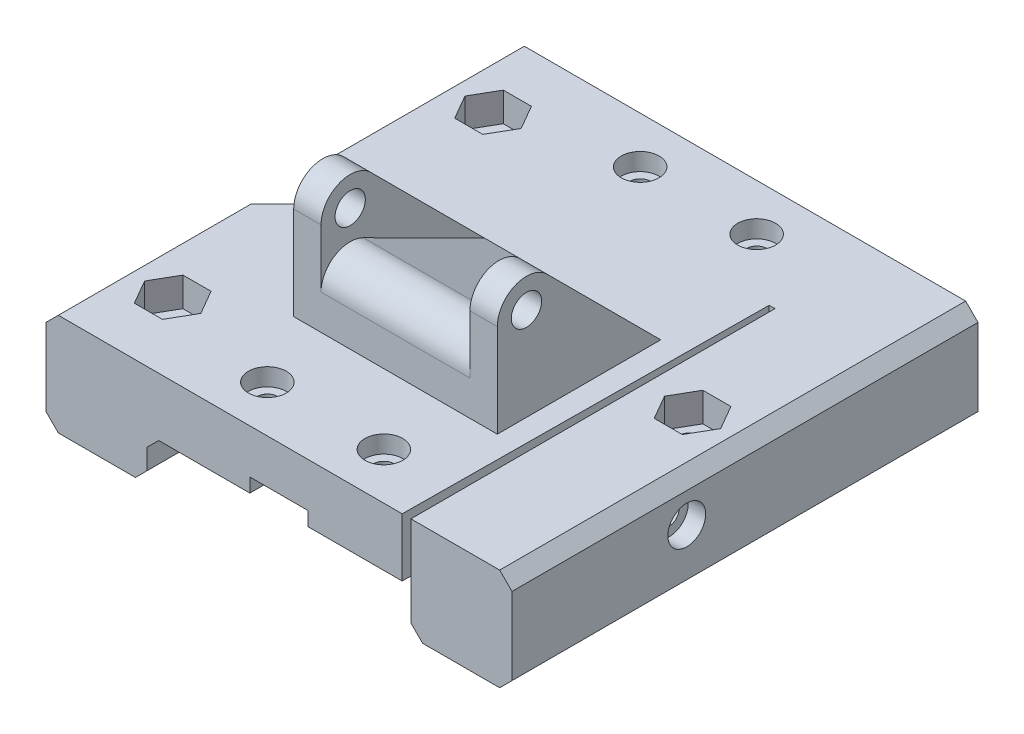
SolidWorks part; units mm, degrees
ref_plane "Front Plane" through (0, 0, 0) normal (0, 0, 1) x (1, 0, 0)
ref_plane "Top Plane" through (0, 0, 0) normal (0, 1, 0) x (1, 0, 0)
ref_plane "Right Plane" through (0, 0, 0) normal (1, 0, 0) x (0, 0, -1)
sketch "Sketch1" plane through (0, 0, 0) normal (0, 0, 1) x (1, 0, 0)
  line L0 (253.1831, 132.1321) -> (251.1831, 130.1321)
  line L1 (296.4801, 132.1321) -> (296.4801, 126.6321)
  line L2 (251.1831, 130.1321) -> (251.1831, 126.6321)
  line L3 (249.1831, 124.6321) -> (251.1831, 126.6321)
  line L4 (296.4801, 126.6321) -> (298.4801, 124.6321)
  line L949 (253.1831, 132.1321) -> (296.4801, 132.1321)
  line L950 (235.9482, 142.1321) -> (311.7151, 142.1321)
  line L1018 (235.9482, 124.6321) -> (249.1831, 124.6321)
  line L1037 (311.7151, 124.6321) -> (298.4801, 124.6321)
  line L1179 (235.9482, 124.6321) -> (233.8316, 126.7487)
  line L1180 (235.9482, 142.1321) -> (233.8316, 140.0155)
  line L1183 (311.7151, 124.6321) -> (313.8316, 126.7487)
  line L1184 (311.7151, 142.1321) -> (313.8316, 140.0155)
  line L1219 (233.8316, 126.7487) -> (233.8316, 140.0155)
  line L1220 (313.8316, 140.0155) -> (313.8316, 126.7487)
  point P2 (296.4801, 132.1321)
  point P3 (296.4801, 124.6321)
  point P4 (251.1831, 132.1321)
  point P5 (251.1831, 124.6321)
  dimension "D1" = 17.5
  dimension "D3" = 2
  dimension "D4" = 2
  dimension "D5" = 2
  dimension "D2" = 17.5
extrude "Boss-Extrude1" add sketch "Sketch1" along normal blind 80
sketch "Sketch2" plane through (0, 142.1321, 0) normal (0, 1, 0) x (1, 0, 0)
  line L0 (273.8316, 0) -> (273.8316, -80) construction
  line L3 (238.4807, -40) -> (314.2475, -40) construction
  circle A0 centre (243.0816, -12.5) radius 2.6
  circle A1 centre (304.5816, -40) radius 2.6
  circle A3 centre (243.0816, -67.5) radius 2.6
  dimension "D1" = 5.2
  dimension "D2" = 30.75
  dimension "D3" = 30.75
extrude "Cut-Extrude1" cut sketch "Sketch2" against normal through all
sketch "Sketch3" plane through (0, 132.1321, 0) normal (0, -1, 0) x (1, 0, 0)
  line L0 (296.4802, 80) -> (294.9802, 80)
  line L1 (296.4801, 80) -> (296.4801, 0) construction
  line L2 (296.4801, 17.5) -> (295.4801, 17.508)
  line L3 (296.4801, 17.5) -> (296.4802, 80)
  line L4 (294.9802, 80) -> (296.4802, 80)
  line L5 (295.4801, 17.508) -> (294.9802, 80)
  point P0 (296.4801, 80)
  point P4 (296.9801, 80.5)
  point P15 (296.9801, 17)
  point P16 (294.9801, 17)
  point P17 (294.9801, 80.5)
  point P19 (296.9801, 80)
  point P20 (296.9762, 17)
  point P22 (297.4841, 80.496)
  point P24 (295.4842, 80.512)
  point P25 (294.9802, 17.512)
  dimension "D1" = 1.5
  dimension "D2" = 1
sketch "Sketch5" plane through (313.8316, 0, 0) normal (1, 0, 0) x (0, 0, -1)
  line L0 (-40, 142.1321) -> (-40, 124.6321) construction
  line L2 (-80, 124.6321) -> (0, 124.6321) construction
  circle A0 centre (-50, 134.9015) radius 3.25
  dimension "D1" = 6.5
  dimension "D2" = 30
  dimension "D3" = 5.114
sketch "Sketch7" plane through (0, 132.1321, 0) normal (0, -1, 0) x (1, 0, 0)
  line L0 (291.4801, 52.875) -> (291.4801, 47.125)
  line L1 (291.4801, 47.125) -> (289.5801, 47.125)
  line L2 (289.5801, 47.125) -> (289.5801, 52.875)
  line L3 (289.5801, 52.875) -> (291.4801, 52.875)
  line L4 (260.0782, 50) -> (295.472, 50) construction
  line L5 (258.0836, 42.875) -> (258.0836, 37.125)
  line L6 (233.8316, 40) -> (313.8316, 40) construction
  line L7 (233.8316, 80) -> (233.8316, 0) construction
  line L8 (313.8316, 80) -> (313.8316, 0) construction
  line L9 (258.0836, 37.125) -> (256.1836, 37.125)
  line L10 (256.1836, 37.125) -> (256.1836, 42.875)
  line L11 (256.1836, 42.875) -> (258.0836, 42.875)
  line L12 (256.1836, 40) -> (258.0836, 40) construction
  line L13 (291.4801, 72.125) -> (291.4801, 50) construction
  dimension "D1" = 5.75
  dimension "D2" = 1.9
  dimension "D3" = 30
  dimension "D4" = 22.3515
  dimension "D5" = 22.352
extrude "Cut-Extrude5" cut sketch "Sketch7" against normal blind 5.75
sketch "Sketch9" plane through (0, 132.1321, 0) normal (0, -1, 0) x (1, 0, 0)
  line L0 (268.8316, 80) -> (268.8316, 60)
  line L1 (268.8316, 0) -> (278.8316, 0)
  line L2 (268.8316, 60) -> (278.8316, 60)
  line L3 (278.8316, 60) -> (278.8316, 80)
  line L4 (268.8316, 80) -> (278.8316, 80)
  line L5 (233.8316, 40) -> (313.8316, 40) construction
  line L6 (233.8316, 80) -> (233.8316, 0) construction
  line L7 (313.8316, 80) -> (313.8316, 0) construction
  line L8 (273.8316, 40) -> (273.8316, 79.96) construction
  line L9 (278.8316, 20) -> (278.8316, 0)
  line L10 (268.8316, 20) -> (278.8316, 20)
  line L11 (268.8316, 0) -> (268.8316, 20)
  dimension "D1" = 20
  dimension "D2" = 10
extrude "Cut-Extrude6" cut sketch "Sketch9" against normal blind 2.4
sketch "Sketch11" plane through (0, 132.1321, 0) normal (0, -1, 0) x (1, 0, 0)
  line L0 (273.8316, 79.96) -> (273.8316, 0.04) construction
  line L4 (233.8316, 80) -> (233.8316, 0) construction
  line L5 (233.8316, 40) -> (313.8316, 40) construction
  line L6 (313.8316, 80) -> (313.8316, 0) construction
  line L8 (235.9482, 80) -> (249.1831, 80) construction
  circle A0 centre (263.8316, 72) radius 1.75
  circle A1 centre (283.8316, 72) radius 1.75
  circle A2 centre (283.8316, 8) radius 1.75
  circle A3 centre (263.8316, 8) radius 1.75
  dimension "D1" = 3.5
  dimension "D2" = 8
  dimension "D3" = 10
extrude "Cut-Extrude7" cut sketch "Sketch11" against normal up to vertex
sketch "Sketch13" plane through (0, 142.1321, 0) normal (0, 1, 0) x (1, 0, 0)
  line L0 (263.8316, -8) -> (283.8316, -8) construction
  line L1 (273.8316, -8) -> (273.8316, -80) construction
  line L3 (233.8316, -40) -> (313.8316, -40) construction
  line L4 (233.8316, -80) -> (233.8316, 0) construction
  line L5 (313.8316, -80) -> (313.8316, 0) construction
  circle A0 centre (263.8316, -8) radius 3.25
  circle A1 centre (283.8316, -8) radius 3.25
  circle A2 centre (283.8316, -72) radius 3.25
  circle A3 centre (263.8316, -72) radius 3.25
  dimension "D1" = 6.5
extrude "Cut-Extrude8" cut sketch "Sketch13" against normal blind 3
sketch "Sketch15" plane through (233.8316, 0, 0) normal (-1, 0, 0) x (0, 0, 1)
  line L2 (31.9389, 142.1321) -> (60, 142.1321)
  line L3 (60, 158.1221) -> (60, 142.1321)
  line L5 (51.4645, 161.6576) -> (31.9389, 142.1321)
  line L6 (80, 142.1321) -> (0, 142.1321) construction
  circle A1 centre (55, 158.1221) radius 2.6
  arc A2 (60, 158.1221) -> (51.4645, 161.6576) centre (55, 158.1221) ccw
  dimension "D2" = 10
  dimension "D3" = 5.2
  dimension "D1" = 25
  dimension "D4" = 15.99
extrude "Boss-Extrude7" add sketch "Sketch15" against normal through all
sketch "Sketch19" plane through (0, 142.1321, 0) normal (0, 1, 0) x (1, 0, 0)
  line L0 (273.8316, -39.7395) -> (273.8316, 0) construction
  line L1 (238.2608, -12.5) -> (240.6712, -16.675)
  line L2 (240.6712, -16.675) -> (245.4921, -16.675)
  line L3 (245.4921, -16.675) -> (247.9025, -12.5)
  line L4 (247.9025, -12.5) -> (245.4921, -8.325)
  line L5 (245.4921, -8.325) -> (240.6712, -8.325)
  line L6 (240.6712, -8.325) -> (238.2608, -12.5)
  line L7 (300.0108, -40) -> (302.4212, -44.175)
  line L8 (302.4212, -44.175) -> (307.2421, -44.175)
  line L9 (307.2421, -44.175) -> (309.6525, -40)
  line L10 (309.6525, -40) -> (307.2421, -35.825)
  line L11 (307.2421, -35.825) -> (302.4212, -35.825)
  line L12 (302.4212, -35.825) -> (300.0108, -40)
  line L15 (235.9482, -40) -> (311.7151, -40) construction
  line L24 (240.6712, -71.675) -> (238.2608, -67.5)
  line L25 (245.4921, -71.675) -> (240.6712, -71.675)
  line L26 (247.9025, -67.5) -> (245.4921, -71.675)
  line L27 (245.4921, -63.325) -> (247.9025, -67.5)
  line L28 (240.6712, -63.325) -> (245.4921, -63.325)
  line L29 (238.2608, -67.5) -> (240.6712, -63.325)
  circle A0 centre (243.0816, -12.5) radius 4.175 construction
  circle A1 centre (304.8316, -40) radius 4.175 construction
  circle A3 centre (243.0816, -67.5) radius 4.175 construction
  dimension "D1" = 8.35
extrude "Cut-Extrude12" cut sketch "Sketch19" against normal blind 5
sketch "Sketch16" plane through (0, 0, 60) normal (0, 0, 1) x (1, 0, 0)
  line L0 (273.8316, 165.582) -> (273.8316, 132.1321) construction
  line L1 (286.6121, 165.582) -> (286.6121, 142.1321)
  line L5 (256.3511, 165.582) -> (256.3511, 142.1321)
  line L6 (261.0511, 165.582) -> (261.0511, 142.1321)
  line L7 (256.3511, 165.582) -> (232.5022, 165.582)
  line L8 (232.5022, 165.582) -> (232.5022, 142.1321)
  line L9 (232.5022, 142.1321) -> (256.3511, 142.1321)
  line L12 (291.3121, 165.582) -> (315.161, 165.582)
  line L14 (315.161, 165.582) -> (315.161, 142.1321)
  line L15 (315.161, 142.1321) -> (291.3121, 142.1321)
  line L16 (291.3121, 142.1321) -> (291.3121, 165.582)
  line L17 (261.0511, 142.1321) -> (286.6121, 142.1321)
  line L19 (286.6121, 165.582) -> (261.0511, 165.582)
  point P6 (257.6805, 165.582)
  point P7 (257.6805, 132.1321)
  dimension "D2" = 4.7
  dimension "D3" = 25.561
  dimension "D1" = 4.7
extrude "Cut-Extrude22" cut sketch "Sketch5" against normal blind 3
sketch "Sketch30" plane through (310.8316, 0, 0) normal (1, 0, 0) x (0, 0, -1)
  circle A0 centre (-50, 134.9015) radius 1.675
  dimension "D1" = 3.35
  dimension "D2" = 5.114
extrude "Cut-Extrude23" cut sketch "Sketch30" against normal blind 25
sketch "Sketch31" plane through (0, 0, 0) normal (0, 0, -1) x (-1, 0, 0)
  line L0 (-296.4801, 132.1321) -> (-296.4801, 130.1321)
  line L1 (-296.4801, 132.1321) -> (-296.4801, 126.6321) construction
  line L3 (-278.8316, 132.1321) -> (-296.4801, 132.1321) construction
  line L4 (-294.4801, 132.1321) -> (-296.4801, 132.1321)
  line L5 (-294.4801, 132.1321) -> (-296.4801, 130.1321)
extrude "Cut-Extrude34" cut sketch "Sketch3" against normal through all
extrude "Boss-Extrude5" add sketch "Sketch31" against normal blind 17.5
extrude "Cut-Extrude35" cut sketch "Sketch16" against normal through all
sketch "Sketch38" plane through (233.8316, 0, 0) normal (-1, 0, 0) x (0, 0, 1)
  line L0 (40, 142.1321) -> (40, 124.6321) construction
  line L1 (80, 142.1321) -> (0, 142.1321) construction
  line L2 (80, 124.6321) -> (0, 124.6321) construction
  line L3 (37, 142.1321) -> (37, 124.6321)
  line L4 (43, 142.1321) -> (43, 124.6321)
  line L5 (37, 142.1321) -> (43, 142.1321)
  line L6 (37, 124.6321) -> (43, 124.6321)
  dimension "D1" = 3
  dimension "D2" = 3
extrude "Cut-Extrude36" cut sketch "Sketch38" against normal blind 6
chamfer "Chamfer1" distance 6 angle 45 1 edges at (233.8316, 133.3821, 43)
chamfer "Chamfer2" distance 6 angle 45 1 edges at (233.8316, 133.3821, 37)
sketch "Sketch37" plane through (239.8316, 0, 0) normal (-1, 0, 0) x (0, 0, 1)
  circle A0 centre (40, 134.9014) radius 1.6
  dimension "D3" = 3.2
  dimension "D1" = 3
  dimension "D2" = 10.2693
extrude "Cut-Extrude29" cut sketch "Sketch37" against normal blind 25
sketch "Sketch39" plane through (256.3511, 0, 0) normal (-1, 0, 0) x (0, 0, 1)
  line L0 (52.7554, 152.59) -> (31.9389, 142.1321)
  line L1 (51.4645, 161.6576) -> (31.9389, 142.1321) construction
  line L2 (31.9389, 142.1321) -> (60, 142.1321) construction
  line L3 (60, 142.1321) -> (60, 148.1221)
  line L6 (31.9389, 142.1321) -> (60, 142.1321)
  arc A1 (60, 148.1221) -> (52.7554, 152.59) centre (55, 148.1221) ccw
extrude "Boss-Extrude8" add sketch "Sketch39" against normal up to surface (30.261 mm away) up to face at (286.6121, 151.7239, 51.1461)
